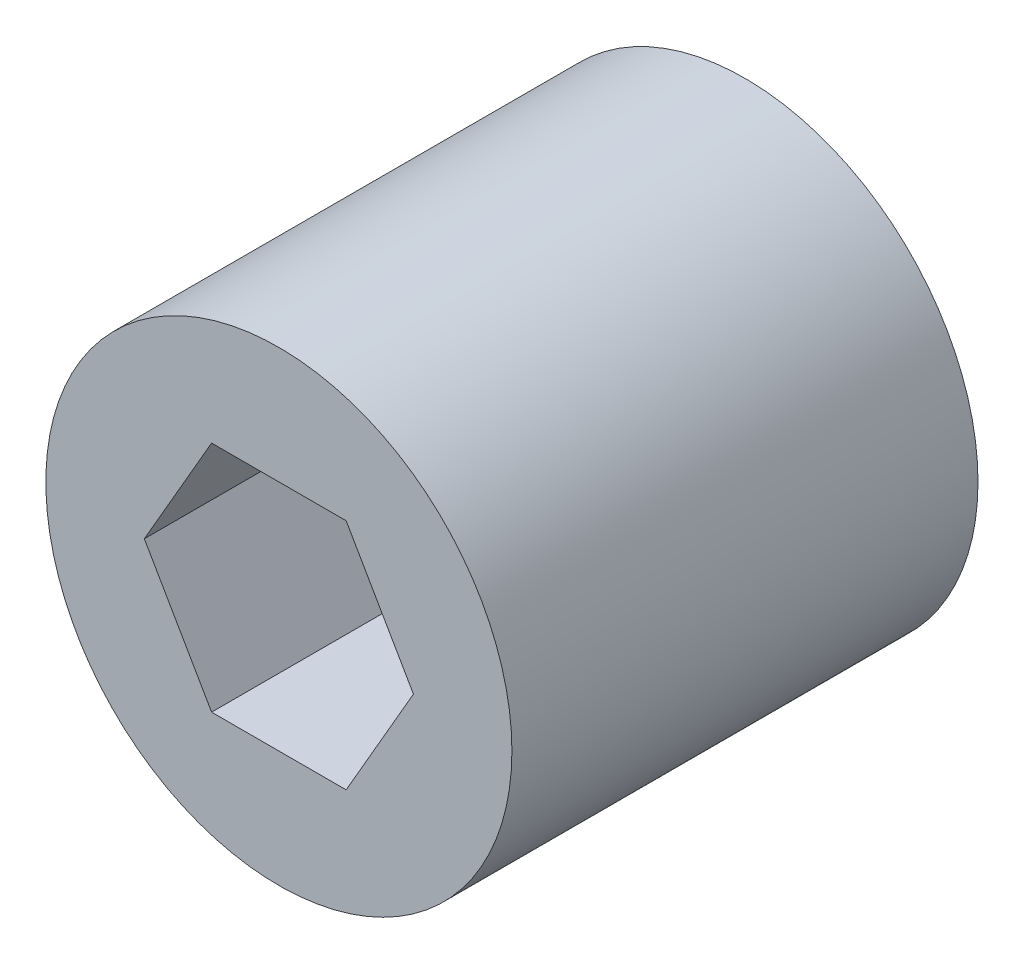
SolidWorks part; units mm, degrees
material "PET"
ref_plane "Front Plane" through (0, 0, 0) normal (0, 0, 1) x (1, 0, 0)
ref_plane "Top Plane" through (0, 0, 0) normal (0, 1, 0) x (1, 0, 0)
ref_plane "Right Plane" through (0, 0, 0) normal (1, 0, 0) x (0, 0, -1)
sketch "Sketch1" plane through (0, 0, 0) normal (0, 0, 1) x (1, 0, 0)
  line L1 (-7.3323, 0) -> (-3.6662, -6.35)
  line L2 (-3.6662, -6.35) -> (3.6662, -6.35)
  line L3 (3.6662, -6.35) -> (7.3323, 0)
  line L4 (7.3323, 0) -> (3.6662, 6.35)
  line L5 (3.6662, 6.35) -> (-3.6662, 6.35)
  line L6 (-3.6662, 6.35) -> (-7.3323, 0)
  circle A0 centre (0, 0) radius 6.35 construction
  circle A1 centre (0, 0) radius 12.7
  dimension "D2" = 25.4
  dimension "D1" = 12.7
extrude "Boss-Extrude1" add sketch "Sketch1" along normal blind 25.4
ref_axis "Axis1" through (0, 0, -13.4694) along (0, 0, 1)
